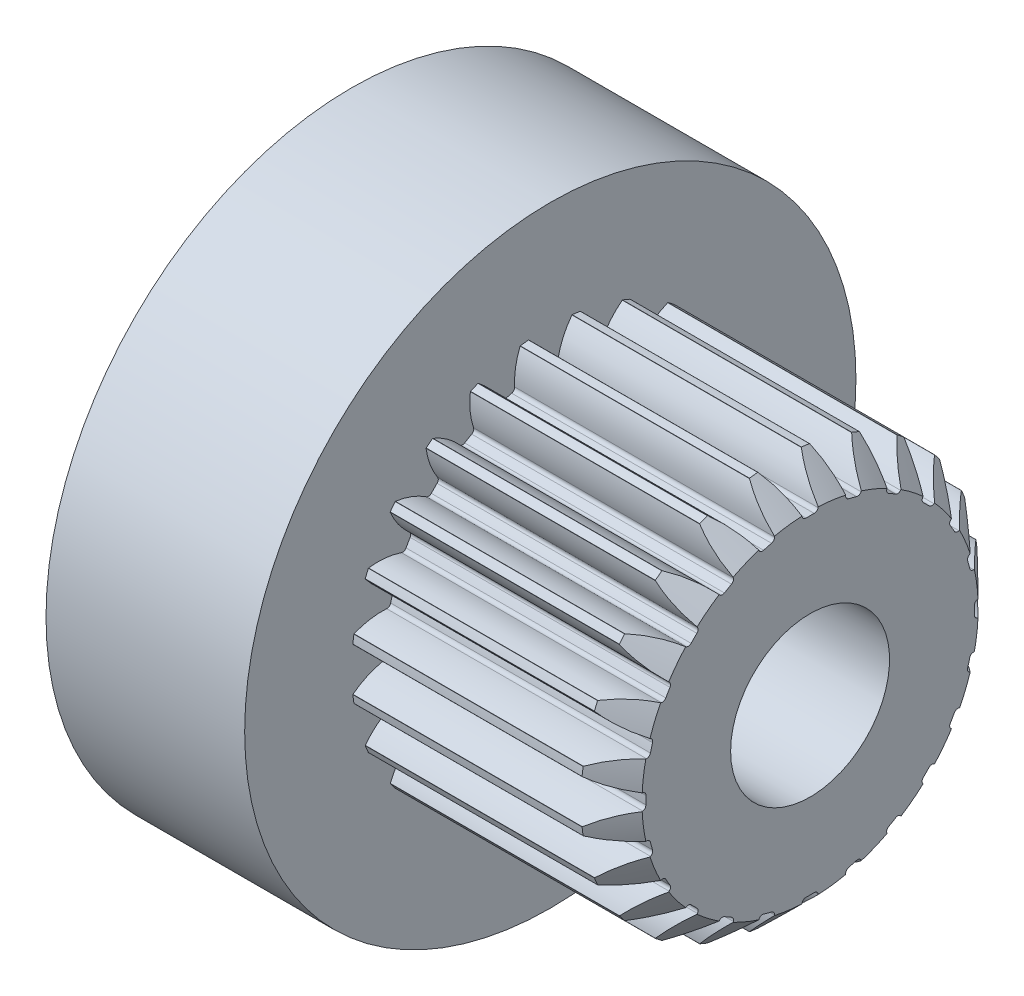
SolidWorks part; units mm, degrees
ref_plane "Plane1" through (0, 0, 0) normal (0, 0, 1) x (1, 0, 0)
ref_plane "Plane2" through (0, 0, 0) normal (0, 1, 0) x (1, 0, 0)
ref_plane "Plane3" through (0, 0, 0) normal (1, 0, 0) x (0, 0, -1)
sketch "HoldingSke" plane through (0, 0, 0) normal (0, 1, 0) x (1, 0, 0)
  line L0 (0, 0) -> (1.8271, -0.8135)
  line L1 (-15, 0) -> (100, 0) construction
  line L2 (0, 0) -> (-2.1039, 2.3779)
  line L3 (0, 0) -> (-11.863, 4.5341)
  line L4 (0, 0) -> (7.8894, 3.5126)
  line L5 (0, 0) -> (-18.7391, -6.9891)
  line L6 (0, 0) -> (-8.2896, -5.593)
  line L7 (-2.1039, 2.3779) -> (2.2011, 21.9091)
  line L8 (-76.2, 54.61) -> (-75.3, 54.61)
  line L9 (-71.009, 38.7566) -> (-53.1078, 45.2721)
  line L10 (-76.2, 71.12) -> (104.1128, 71.12)
  line L11 (0, 0) -> (-10, 0)
  line L12 (-76.2, 101.6) -> (-76.181, 101.6)
  line L13 (24.9733, 27.94) -> (52.9518, 28.4284)
  line L14 (24.9733, 27.94) -> (24.9743, 27.94)
  line L15 (24.9733, 27.94) -> (100.4006, 29.5858)
  line L16 (-63.627, -0.5) -> (-12.827, -0.5)
  circle A0 centre (0, 0) radius 2.5
  circle A1 centre (0, 0) radius 5
  circle A2 centre (0, 0) radius 5
  circle A3 centre (0, 0) radius 2.5
  dimension "Num_teeth" = 24
  dimension "Pitch_radius" = 180.3128
  dimension "Width" = 10
sketch "BasProSke" plane through (0, 0, 0) normal (0, 1, 0) x (1, 0, 0)
  line L0 (-10, 0) -> (60, 0) construction
  line L1 (0, 0) -> (0, 6.5)
  line L2 (0, 0) -> (8.5, 0)
  line L3 (8.5, 0) -> (8.5, 6.5)
  line L4 (8.5, 6.5) -> (0, 6.5)
  dimension "Thickness" = 8.5
  dimension "Diameter" = 13
revolve "Base-Revolve" add sketch "BasProSke" angle 360 about L0
sketch "TooCutSke" plane through (0, 0, 0) normal (1, 0, 0) x (0, 0, -1)
  line L1 (0, 0) -> (0, 107) construction
  line L2 (0, 0) -> (-0.4257, 5.9849) construction
  line L3 (0, 0) -> (-1.5635, 11.876) construction
  line L4 (-0.4257, 5.9849) -> (-0.7818, 5.938) construction
  arc A0 (0.2416, 5.3686) -> (-0.2416, 5.3686) centre (0, 0) ccw
  arc A1 (0.7297, 6.4845) -> (-0.7297, 6.4845) centre (0, 0) ccw
  circle A2 centre (0, 0) radius 6 construction
  circle A3 centre (0, 0) radius 5.6382 construction
  arc A4 (-0.2416, 5.3686) -> (-0.7297, 6.4845) centre (-2.6126, 4.9963) ccw
  arc A5 (0.7297, 6.4845) -> (0.2416, 5.3686) centre (2.6126, 4.9963) ccw
extrude "ToothCut" cut sketch "TooCutSke" along normal through all
fillet "Breaks" radius 0.01 2 edges at (4.25, 6.461, -0.7113) (4.25, 6.461, 0.7113) tangent propagation no
fillet "RootFillets" radius 0.126 2 edges at (4.25, 5.3686, -0.2416) (4.25, 5.3686, 0.2416)
pattern_circular "TeethCuts" count 24 every 15 about axis through (-10, 0, 0) along (1, 0, 0) of "ToothCut", "RootFillets", "Breaks"
sketch "HubNeaOneSke" plane through (0, 0, 0) normal (-1, 0, 0) x (0, 0, 1)
  circle A0 centre (0, 0) radius 5
  dimension "Diameter" = 10
extrude "HubNearOne" add sketch "HubNeaOneSke" along normal blind 6.5001
sketch "HubNeaBotSke" plane through (0, 0, 0) normal (-1, 0, 0) x (0, 0, 1)
  circle A0 centre (0, 0) radius 5
  dimension "Diameter" = 10
extrude "HubNearBoth" [suppressed] add sketch "HubNeaBotSke" along normal blind 5.75
ref_plane "FarPln" through (8.5, 0, 0) normal (1, 0, 0) x (0, 0, -1)
sketch "HubFarSke" plane through (8.5, 0, 0) normal (1, 0, 0) x (0, 0, -1)
  circle A0 centre (0, 0) radius 5
  dimension "Diameter" = 10
extrude "HubFar" [suppressed] add sketch "HubFarSke" along normal blind 5.75
sketch "BorSke" plane through (0, 0, 0) normal (1, 0, 0) x (0, 0, -1)
  circle A0 centre (0, 0) radius 2.6
  dimension "D1" = 5.2
extrude "Bore" cut sketch "BorSke" along normal mid plane 40.0001
sketch "KeySke" plane through (0, 0, 0) normal (1, 0, 0) x (0, 0, -1)
  line L0 (-1, 0) -> (-1, 3.4)
  line L1 (-1, 3.4) -> (1, 3.4)
  line L2 (1, 3.4) -> (1, 0)
  line L3 (0, 0) -> (0, 34) construction
  line L4 (-1, 0) -> (1, 0)
  dimension "Width" = 2
extrude "Keyway" [suppressed] cut sketch "KeySke" along normal mid plane 40.0001
pattern_circular "Keyway2" [suppressed] count 2 every 90 about axis through (-10, 0, 0) along (1, 0, 0) reverse direction yes
sketch "Sketch1" plane through (-6.5001, 0, 0) normal (-1, 0, 0) x (0, 0, 1)
  circle A0 centre (0, 0) radius 2.6 construction
  circle A1 centre (0, 0) radius 2.6
  circle A2 centre (0, 0) radius 10
  dimension "D1" = 20
extrude "Boss-Extrude1" add sketch "Sketch1" against normal up to surface (6.5001 mm away) up to face at (0, 0, -5)
sketch "Sketch2" [suppressed] plane through (0, 0, 0) normal (0, 1, 0) x (1, 0, 0)
  line L0 (5, 0) -> (-10.0001, 0) construction
  line L1 (-10.0001, 7.5) -> (-10.0001, -7.5) construction
  line L2 (5, 6.4249) -> (5, 0) construction
  line L3 (10, 6.4249) -> (0, 6.4249) construction
  circle A0 centre (5, 0) radius 1.6
  dimension "D1" = 3.2
extrude "Cut-Extrude3" [suppressed] cut sketch "Sketch2" against normal through all contours A0
sketch "Sketch3" plane through (-6.5001, 0, 0) normal (-1, 0, 0) x (0, 0, 1)
  line L1 (-2.7074, -5.5177) -> (2.7926, -5.5177)
  line L2 (-2.7074, -5.5177) -> (-2.7074, -3.5177)
  line L3 (-2.7074, -3.5177) -> (2.7926, -3.5177)
  line L4 (2.7926, -5.5177) -> (2.7926, -3.5177)
  line L5 (-2.7074, -5.5177) -> (2.7926, -3.5177) construction
  line L6 (-2.7074, -3.5177) -> (2.7926, -5.5177) construction
  point P0 (0.0426, -4.5177)
  dimension "D1" = 5.5
  dimension "D2" = 2
ref_plane "Plane4" through (0, -2.6, 0) normal (0, 1, 0) x (1, 0, 0)
sketch "Sketch4" [suppressed] plane through (0, 0, 0) normal (0, 1, 0) x (1, 0, 0)
  line L0 (-10.0001, 7.5) -> (-10.0001, -7.5) construction
  line L1 (-10.0001, -2.75) -> (7.6, -2.75)
  line L2 (-10.0001, -2.75) -> (-10.0001, 2.75)
  line L3 (-10.0001, 2.75) -> (7.6, 2.75)
  line L4 (7.6, -2.75) -> (7.6, 2.75)
  line L5 (-10.0001, -2.75) -> (7.6, 2.75) construction
  line L6 (-10.0001, 2.75) -> (7.6, -2.75) construction
  circle A0 centre (5, 0) radius 1.6 construction
  circle A1 centre (5, 0) radius 1.6
  point P0 (-1.2, 0)
  dimension "D1" = 2.6
  dimension "D2" = 5.5
extrude "Cut-Extrude4" [suppressed] cut sketch "Sketch4" against normal blind 1 and the other way blind 1 from surface starting at plane "Plane4"
sketch "Sketch5" plane through (0, 0, 0) normal (0, 1, 0) x (1, 0, 0)
  line L0 (0, 0) -> (14.7495, 0) construction
  line L1 (0, -0.1338) -> (0, 0.1338) construction
  line L2 (7.5, 6.5) -> (8.5, 5.5)
  line L3 (8.5, 5.5) -> (8.5, 6.5)
  line L4 (8.5, 6.5) -> (7.5, 6.5)
  line L5 (8.5, 4.8702) -> (8.5, 5.9454) construction
  dimension "D1" = 6.5
  dimension "D2" = 1
revolve "Cut-Revolve1" cut sketch "Sketch5" angle 360 about L0
sketch "Sketch6" plane through (0, 0, 0) normal (1, 0, 0) x (0, 0, -1)
  circle A0 centre (0, 0) radius 10 construction
  circle A1 centre (0, 0) radius 10
extrude "Cut-Extrude6" [suppressed] cut sketch "Sketch6" against normal through all
sketch "Sketch7" plane through (0, 0, 0) normal (0, 1, 0) x (1, 0, 0)
  line L0 (-3.25, 10) -> (-3.25, 0) construction
  line L1 (0, 10) -> (-6.5001, 10) construction
  line L2 (-3.25, 0) -> (0, 0) construction
  line L3 (0, -0.1338) -> (0, 0.1338) construction
  circle A0 centre (-3.25, 0) radius 1.8
  dimension "D1" = 3.6
extrude "Cut-Extrude7" cut sketch "Sketch7" against normal through all
ref_plane "Plane5" through (-3.25, 0, 0) normal (-1, 0, 0) x (0, 0, 1)
sketch "Sketch8" plane through (-3.25, 0, 0) normal (-1, 0, 0) x (0, 0, 1)
  line L0 (0, -2.6) -> (0, -10) construction
  line L2 (-2.75, -6.2) -> (2.75, -6.2)
  line L3 (-2.75, -6.2) -> (-2.75, -4.1)
  line L4 (-2.75, -4.1) -> (2.75, -4.1)
  line L5 (2.75, -6.2) -> (2.75, -4.1)
  line L6 (-2.75, -6.2) -> (2.75, -4.1) construction
  line L7 (-2.75, -4.1) -> (2.75, -6.2) construction
  arc A0 (-1.8, -1.8762) -> (1.8, -1.8762) centre (0, 0) ccw construction
  arc A1 (-1.8, -1.8762) -> (1.8, -1.8762) centre (0, 0) ccw construction
  circle A2 centre (0, 0) radius 10 construction
  point P7 (0, -5.15)
  point P12 (0, -4.8784)
  dimension "D1" = 2.1
  dimension "D2" = 5.5
  dimension "D3" = 1.5
extrude "Cut-Extrude8" cut sketch "Sketch8" against normal mid plane 5 contours L4 L3 L2 L0 region at (-3.25, -5.15, 0)
sketch "Sketch9" plane through (-5.75, 0, 0) normal (1, 0, 0) x (0, 0, -1)
  line L4 (-2.75, -6.2) -> (2.75, -6.2)
  line L5 (2.75, -6.2) -> (2.75, -4.1)
  line L6 (2.75, -4.1) -> (-2.75, -4.1)
  line L7 (-2.75, -4.1) -> (-2.75, -6.2)
  line L8 (-2.75, -6.2) -> (2.75, -6.2)
  line L9 (2.75, -6.2) -> (2.75, -4.1)
  line L10 (2.75, -4.1) -> (-2.75, -4.1)
  line L11 (-2.75, -4.1) -> (-2.75, -6.2)
  dimension "D1" = 0
extrude "Cut-Extrude9" cut sketch "Sketch9" against normal through all
equation "' \"Module@HoldingSke\" = 6.35"
equation "' \"Num_teeth@HoldingSke\" = 12"
equation "' \"Ap@HoldingSke\" =  20"
equation "' \"Ap@HoldingSke\" = 20"
equation "' \"Width@HoldingSke\" = 0.5 * 25.4"
equation "' \"Hub_dia@HoldingSke\"= 1 * 25.4"
equation "' \"Hub_dia@HoldingSke\" = 1 * 25.4"
equation "' \"Overall_len@HoldingSke\" = 1.0 * 25.4"
equation "' \"Bore@HoldingSke\" = 0.75 * 25.4"
equation "' \"T_dim@HoldingSke\" = 0.1 * 25.4"
equation "' \"Width@KeySke\" = 0.25 * 25.4"
equation "' \"Show_teeth@HoldingSke\" = 13"
equation "' \"Backlash@HoldingSke\" = 0.009 * 25.4"
equation "' \"Addendum_fac@HoldingSke\" = 1.0"
equation "' \"Dedendum_fac@HoldingSke\" = 1.25"
equation "' \"Dedendum_add@HoldingSke\" = 0.00005 * 25.4"
equation "' \"Clearance_fac@HoldingSke\" = 0.25"
equation "\"Pitch@HoldingSke\" = 1 / \"Module@HoldingSke\""
equation "\"Overcut_dia@TooCutSke\" = (\"Num_teeth@HoldingSke\" + 2 * \"Addendum_fac@HoldingSke\") / \"Pitch@HoldingSke\" + 0.002 * 25.4"
equation "\"Pitch_dia@TooCutSke\" = \"Num_teeth@HoldingSke\" / \"Pitch@HoldingSke\""
equation "\"Base_dia@TooCutSke\" = \"Num_teeth@HoldingSke\" / \"Pitch@HoldingSke\" * cos((\"Ap@HoldingSke\"  * 3.14159265 / 180))"
equation "\"Root_dia@TooCutSke\" = (\"Num_teeth@HoldingSke\" + 2) / \"Pitch@HoldingSke\" - 2 * (\"Addendum_fac@HoldingSke\" + \"Dedendum_fac@HoldingSke\") / \"Pitch@HoldingSke\" - \"Dedendum_add@HoldingSke\" * 2"
equation "\"Half_ang@TooCutSke\" = 180 / \"Num_teeth@HoldingSke\""
equation "\"Half_CT@TooCutSke\" = \"Num_teeth@HoldingSke\" / \"Pitch@HoldingSke\" * sin((3.14159265 / 2 / \"Num_teeth@HoldingSke\")) / 2 - 7 * \"Backlash@HoldingSke\" / 4"
equation "\"Flank_rad@TooCutSke\" = \"Num_teeth@HoldingSke\" / \"Pitch@HoldingSke\" / 5"
equation "\"Radius@RootFillets\" = \"Clearance_fac@HoldingSke\" / \"Pitch@HoldingSke\" + \"Dedendum_add@HoldingSke\""
equation "\"Break_rad@Breaks\" = 0.02 / \"Pitch@HoldingSke\""
equation "\"Thickness@HoldingSke\" = \"Width@HoldingSke\""
equation "\"OAL@HoldingSke\" = \"Thickness@HoldingSke\""
equation "\"MHD@HoldingSke\" = (\"Num_teeth@HoldingSke\" + 2) / \"Pitch@HoldingSke\" - 2 * (\"Addendum_fac@HoldingSke\" + \"Dedendum_fac@HoldingSke\")  / \"Pitch@HoldingSke\" - \"Dedendum_add@HoldingSke\" * 2"
equation "\"MBD@HoldingSke\" = (\"Num_teeth@HoldingSke\" + 2) / \"Pitch@HoldingSke\" - 2 * (\"Addendum_fac@HoldingSke\" + \"Dedendum_fac@HoldingSke\")  / \"Pitch@HoldingSke\" - \"Dedendum_add@HoldingSke\" * 2 - 0.002 * 25.4"
equation "\"MHD@HoldingSke\" = ((sgn( \"MHD@HoldingSke\" - \"Hub_dia@HoldingSke\" )-1)*( \"MHD@HoldingSke\" - \"Hub_dia@HoldingSke\" ))/-2+ \"Hub_dia@HoldingSke\""
equation "\"MBD@HoldingSke\" = ((sgn( \"MBD@HoldingSke\" - \"Bore@HoldingSke\" )-1)*( \"MBD@HoldingSke\" - \"Bore@HoldingSke\" ))/-2+ \"Bore@HoldingSke\""
equation "\"OAL@HoldingSke\" = ((sgn( \"OAL@HoldingSke\" - \"Overall_len@HoldingSke\" )+1)*( \"OAL@HoldingSke\" - \"Overall_len@HoldingSke\" ))/2 + \"Overall_len@HoldingSke\" + 0.000002 * 25.4"
equation "\"Num_teeth@TeethCuts\" = int( \"Show_teeth@HoldingSke\" ) + 1"
equation "\"Num_teeth@TeethCuts\" = ((sgn( \"Num_teeth@TeethCuts\" - \"Num_teeth@HoldingSke\" )-1)*( \"Num_teeth@TeethCuts\" - \"Num_teeth@HoldingSke\" ))/-2+ \"Num_teeth@HoldingSke\""
equation "\"Num_teeth@TeethCuts\" = ((sgn( \"Num_teeth@TeethCuts\" - 2.0)+1)*( \"Num_teeth@TeethCuts\" - 2.0))/2 +2.0"
equation "\"Angle@TeethCuts\" = 360.0 / \"Num_teeth@HoldingSke\""
equation "\"Diameter@BasProSke\" = (\"Num_teeth@HoldingSke\" + 2 * \"Addendum_fac@HoldingSke\") / \"Pitch@HoldingSke\""
equation "\"Thickness@BasProSke\"=8.5"
equation "' \"Fillet_rad@BasProSke\" =  \"Thickness@HoldingSke\" * 0.05"
equation "' \"Fillet_rad@BasProSke\" = \"Thickness@HoldingSke\" * 0.05"
equation "\"MHD@HoldingSke\" = ((sgn( \"MHD@HoldingSke\" - \"Root_dia@TooCutSke\" )-1)*( \"MHD@HoldingSke\" - \"Root_dia@TooCutSke\" ))/-2+ \"Root_dia@TooCutSke\""
equation "\"Diameter@HubNeaOneSke\" = \"MHD@HoldingSke\""
equation "\"Length@HubNearOne\"=\"OAL@HoldingSke\" - \"Thickness@BasProSke\" - 5"
equation "\"Diameter@HubNeaBotSke\" = \"MHD@HoldingSke\""
equation "\"Length@HubNearBoth\" = ( \"OAL@HoldingSke\" - \"Thickness@BasProSke\" ) / 2.0"
equation "\"Thickness@FarPln\" = \"Thickness@BasProSke\""
equation "\"Diameter@HubFarSke\" = \"MHD@HoldingSke\""
equation "\"Length@HubFar\" = ( \"OAL@HoldingSke\" - \"Thickness@BasProSke\" ) / 2.0"
equation "\"D1@Bore\" = \"OAL@HoldingSke\" * 2.0"
equation "\"D1@Keyway\" = \"OAL@HoldingSke\" * 2.0"
equation "\"Offset@KeySke\" = \"T_dim@HoldingSke\" + \"MBD@HoldingSke\" / 2.0"
